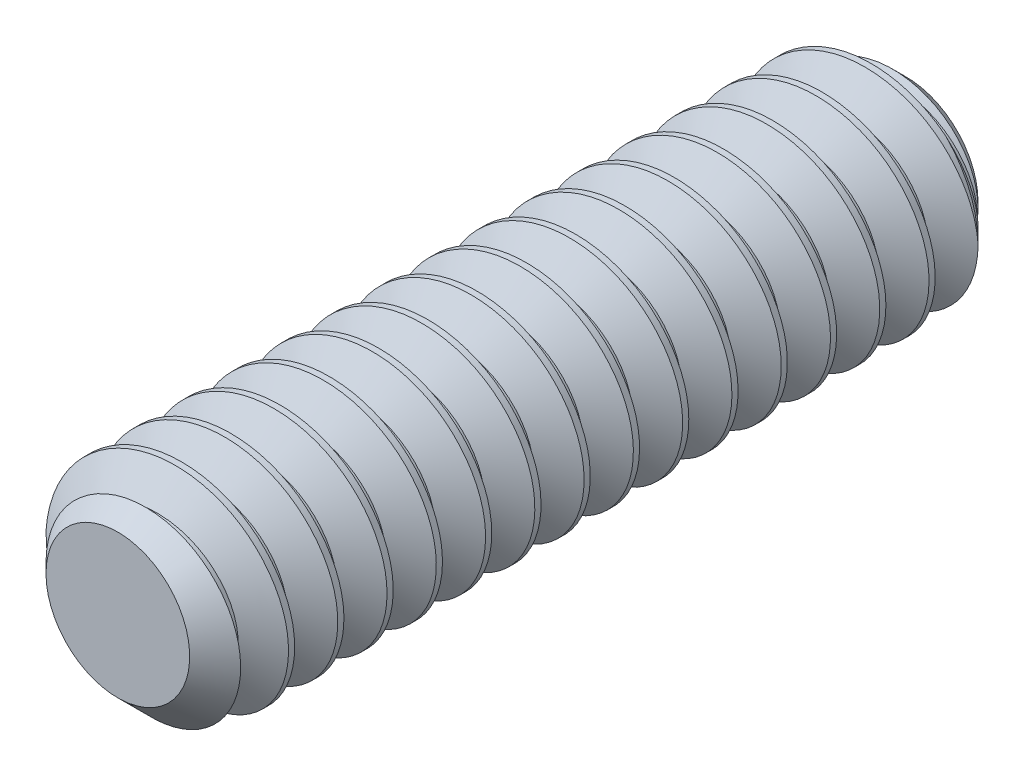
SolidWorks part; units mm, degrees
ref_plane "Front Plane" through (0, 0, 0) normal (0, 0, 1) x (1, 0, 0)
ref_plane "Top Plane" through (0, 0, 0) normal (0, 1, 0) x (1, 0, 0)
ref_plane "Right Plane" through (0, 0, 0) normal (1, 0, 0) x (0, 0, -1)
sketch "Sketch1" plane through (0, 0, 0) normal (1, 0, 0) x (0, 0, -1)
  line L0 (-6.35, 0) -> (6.35, 0) construction
  line L1 (6.35, 1.7526) -> (6.35, -1.7526) construction
  line L2 (-6.35, 1.7526) -> (-6.35, -1.7526) construction
  line L3 (-6.35, 1.7526) -> (-5.5562, 1.7526) construction
  line L4 (7.1437, 1.7526) -> (7.1437, -1.7526) construction
  line L5 (0.3099, 1.7526) -> (0.3099, -1.7526) construction
  line L6 (-0.3099, 1.7526) -> (-0.3099, -1.7526) construction
  line L8 (-6.35, -1.7526) -> (-4.3656, -1.7526) construction
  point P11 (7.1437, 0)
  point P14 (0.3099, 0)
  point P17 (-0.3099, 0)
  dimension "Thread Size" = 3.5052
  dimension "Length" = 12.7
  dimension "Pitch" = 0.7937
  dimension "SegmentLength" = 13.4937
  dimension "D3" = 1.9844
  dimension "D1" = 6.6599
  dimension "D2" = 6.6599
sketch "Sketch2" plane through (0, 0, 0) normal (1, 0, 0) x (0, 0, -1)
  line L0 (0, 12.2238) -> (0, -12.2238) construction
  line L1 (6.35, 1.7526) -> (-6.35, 1.7526)
  line L2 (6.35, 1.7526) -> (6.35, 0)
  line L3 (6.35, 0) -> (-6.35, 0)
  line L4 (-6.35, 1.7526) -> (-6.35, 0)
  line L5 (0, 0) -> (0, 1.7526) construction
  line L6 (6.35, 0.8763) -> (-6.35, 0.8763) construction
  line L7 (-6.35, 0) -> (6.35, 0) construction
  point P152 (0, 0.8763)
revolve "Revolve1" add sketch "Sketch2" angle 360 about L0
chamfer "Chamfer1" distance 0.5953 angle 45 2 edges at (1.7526, 0, -6.35) (1.7526, 0, 6.35)
ref_axis "Center Axis 1" through (0, 0, 6.35) along (0, 0, -1)
sketch "Sketch3" plane through (0, 0, 6.35) normal (0, 0, 1) x (1, 0, 0)
  circle A0 centre (0, 0) radius 1.7526
  dimension "D1" = 3.5052
curve "Helix/Spiral1" pitch 0.7937 height 13.4937 radius 1.7526 centre (0, 0, 6.35) axis (0, 0, -1) start towards (0, 1, 0)
sketch "Sketch4" plane through (0, 0, 0) normal (1, 0, 0) x (0, 0, -1)
  line L0 (-6.3004, 1.8385) -> (-6.6973, 1.1511) construction
  line L1 (-6.6973, 1.1511) -> (-7.0941, 1.8385) construction
  line L2 (-6.3004, 1.8385) -> (-7.0941, 1.8385) construction
  line L3 (-6.6477, 1.237) -> (-6.7469, 1.237) construction
  line L4 (-6.6973, 1.237) -> (-6.6973, 1.1511) construction
  line L5 (-6.35, 1.7526) -> (-7.0445, 1.7526) construction
  line L6 (-6.6973, 1.8385) -> (-6.6973, 1.7526) construction
  line L7 (-6.3252, 1.7956) -> (-7.0693, 1.7956) construction
  line L8 (-6.3252, 1.7956) -> (-7.0693, 1.7956)
  line L9 (-7.0693, 1.7956) -> (-6.7469, 1.237)
  line L10 (-6.7469, 1.237) -> (-6.6477, 1.237)
  line L11 (-6.6477, 1.237) -> (-6.3252, 1.7956)
  point P13 (-6.6973, 1.7956)
  dimension "D1" = 60
  dimension "D2" = 0.7937
  dimension "D3" = 0.0992
sweep "Cut-Sweep1" cut profiles "Sketch4" path "Helix/Spiral1"
equation "\"SegmentLength@Sketch1\"= \"Pitch@Sketch1\" * 17"
equation "\"D1@Chamfer1\"=\"Pitch@Sketch1\"*.75"
equation "\"D1@Sketch3\" = \"Thread Size@Sketch1\""
equation "\"D2@Sketch4\" = \"Pitch@Sketch1\""
equation "\"D3@Sketch4\"=\"D2@Sketch4\"/8"
equation "\"D4@Helix/Spiral1\" = \"Pitch@Sketch1\""
equation "\"D3@Helix/Spiral1\"=\"Length@Sketch1\"+\"Pitch@Sketch1\""
equation "\"D3@Sketch1\"=\"Pitch@Sketch1\"*2.5"
equation "\"D1@Sketch1\"=\"Thread Size@Sketch1\"*1.9"
equation "\"D2@Sketch1\"=\"Thread Size@Sketch1\"*1.9"
